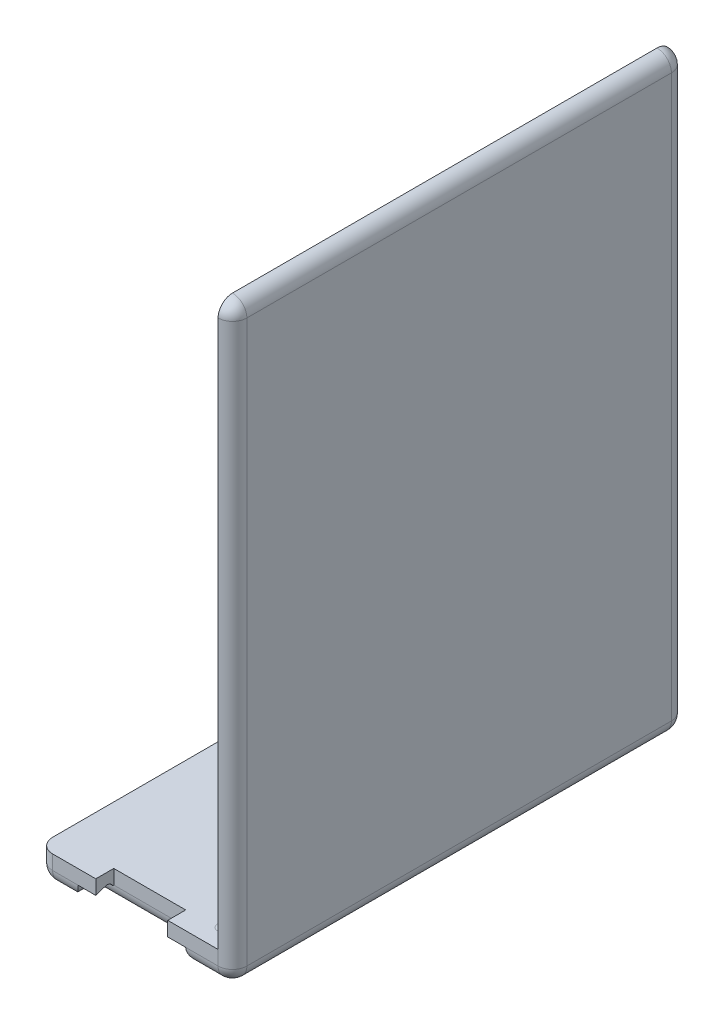
SolidWorks part; units mm, degrees
note: The reader was unsure of these and kept them because the rebuilt part matched: shared geometry of "Sketch6<3>".
ref_plane "Front Plane" through (0, 0, 0) normal (0, 0, 1) x (1, 0, 0)
ref_plane "Top Plane" through (0, 0, 0) normal (0, 1, 0) x (1, 0, 0)
ref_plane "Right Plane" through (0, 0, 0) normal (1, 0, 0) x (0, 0, -1)
sketch "Sketch1" plane through (0, 0, 0) normal (0, 1, 0) x (1, 0, 0)
  line L1 (0, 0) -> (-25, 0)
  line L2 (0, 0) -> (0, -63)
  line L3 (0, -63) -> (-25, -63)
  line L4 (-25, 0) -> (-25, -63)
  dimension "D1" = 63
  dimension "D2" = 25
extrude "Boss-Extrude1" add sketch "Sketch1" along normal blind 4
sketch "Sketch3" plane through (0, 0, 0) normal (1, 0, 0) x (0, 0, -1)
  line L1 (-63, 0) -> (0, 0)
  line L2 (-63, 0) -> (-63, 4)
  line L3 (-63, 4) -> (0, 4)
  line L4 (0, 0) -> (0, 4)
extrude "Boss-Extrude2" add sketch "Sketch3" along normal blind 2
sketch "Sketch4" plane through (0, 4, 0) normal (0, 1, 0) x (1, 0, 0)
  line L1 (2, -63) -> (0, -63)
  line L2 (2, -63) -> (2, 0)
  line L3 (2, 0) -> (0, 0)
  line L4 (0, -63) -> (0, 0)
extrude "Boss-Extrude3" add sketch "Sketch4" along normal blind 78
sketch "Sketch6" plane through (0, 0, 0) normal (0, -1, 0) x (1, 0, 0)
  line L0 (-25, 63) -> (2, 63) construction
  line L1 (-7, 63) -> (-17, 63)
  line L2 (-7, 63) -> (-7, 60.5)
  line L3 (-7, 60.5) -> (-17, 60.5)
  line L4 (-17, 63) -> (-17, 60.5)
  line L5 (2, 0) -> (-25, 0) construction
  line L6 (-7, 0) -> (-17, 0)
  line L7 (-7, 0) -> (-7, 2.5)
  line L8 (-7, 2.5) -> (-17, 2.5)
  line L9 (-17, 0) -> (-17, 2.5)
  line L10 (-25, 0) -> (-25, 63) construction
  dimension "D1" = 2.5
  dimension "D2" = 2.5
  dimension "D3" = 10
  dimension "D4" = 10
  dimension "D5" = 8
  dimension "D6" = 8
extrude "Cut-Extrude1" cut sketch "Sketch6" against normal through all contours L8 L9 L6 L7
extrude "Cut-Extrude2" cut sketch "Sketch6<3>" against normal blind 80 contours L3 L4 L1 L2
sketch "Sketch6<3>" plane through (0, 0, 0) normal (0, -1, 0) x (1, 0, 0) same geometry as "Sketch6"
sketch "Sketch8" plane through (0, 0, 63) normal (0, 0, 1) x (1, 0, 0)
  line L0 (-7, 0) -> (2, 0) construction
  line L1 (-4.5, 0) -> (-19.5, 0)
  line L2 (-4.5, 0) -> (-4.5, 2)
  line L3 (-4.5, 2) -> (-19.5, 2)
  line L4 (-19.5, 0) -> (-19.5, 2)
  line L5 (-25, 4) -> (-25, 0) construction
  dimension "D1" = 2
  dimension "D2" = 15
  dimension "D3" = 5.5
extrude "Cut-Extrude3" cut sketch "Sketch8" against normal blind 2.5
sketch "Sketch9" plane through (-4.5, 0, 0) normal (-1, 0, 0) x (0, 0, 1)
  line L0 (63, 0) -> (63, 2) construction
  line L1 (60.5, 2) -> (63, 2) construction
  line L2 (61.5, 2.5) -> (63, 2)
  line L3 (63, 2) -> (61.5, 2)
  line L4 (61.5, 2) -> (61.5, 2.5)
  circle A0 centre (61.5, 1.5) radius 1
  line M3 (63, 2) -> (60.5, 2)
  dimension "D1" = 2
  dimension "D2" = 1.5
  dimension "D3" = 0.5
extrude "Cut-Extrude5" cut sketch "Sketch9" along a picked direction on the side of the normal blind 15 contours A0 L3 M3 | L4 A0 M3
sketch "Sketch10" plane through (0, 0, 0) normal (0, -1, 0) x (1, 0, 0)
  line L0 (2, 31.5) -> (-25, 31.5) construction
  line L1 (2, 63) -> (2, 0) construction
  line L2 (-25, 0) -> (-25, 63) construction
  line L3 (-25, 31.5) -> (2, 31.5) construction
sketch "Sketch11" plane through (0, 0, 0) normal (0, 0, -1) x (-1, 0, 0)
  line L0 (-2, 0) -> (7, 0) construction
  line L1 (4.5, 0) -> (19.5, 0)
  line L2 (4.5, 0) -> (4.5, 2)
  line L3 (4.5, 2) -> (19.5, 2)
  line L4 (19.5, 0) -> (19.5, 2)
  line L5 (25, 4) -> (25, 0) construction
  dimension "D1" = 2
  dimension "D2" = 15
  dimension "D3" = 5.5
extrude "Cut-Extrude6" cut sketch "Sketch11" against normal blind 3 contours L2 L3 L4 L1
sketch "Sketch12" plane through (-4.5, 0, 0) normal (-1, 0, 0) x (0, 0, 1)
  line L0 (0, 0) -> (0, 2) construction
  line L1 (3, 2) -> (0, 2) construction
  line L2 (1.9, 2.5) -> (0, 2)
  line L3 (0, 2) -> (1.9, 2)
  line L4 (1.9, 2) -> (1.9, 2.5)
  circle A0 centre (1.9, 1.5) radius 1
  line M4 (3, 2) -> (0, 2)
  dimension "D1" = 2
  dimension "D2" = 1.9
  dimension "D3" = 0.5
extrude "Cut-Extrude7" cut sketch "Sketch12" along normal blind 15 contours A0 M4 | A0 L4 M4
fillet "Fillet6" radius 2 20 edges at (-22.25, 0, 0) (-12, 0, 3) (-19.5, 0, 1.5) (-4.5, 1, 0) (-4.5, 0, 1.5) (-19.5, 1, 3) (-4.5, 1, 3) (-19.5, 1, 0) (2, 0, 31.5) (-22.25, 0, 63) (-25, 0, 31.5) (-1.25, 0, 0) (-12, 0, 60.5) (-1.25, 0, 63) (-19.5, 1, 63) (-4.5, 1, 60.5) (-4.5, 0, 61.75) (-19.5, 1, 60.5) (-19.5, 0, 61.75) (-4.5, 1, 63)
fillet "Fillet7" radius 2 4 edges at (-24.4142, 0.5858, 62.4142) (-24.4142, 0.5858, 0.5858) (-25, 3, 63) (-25, 3, 0)
sketch "Sketch13" plane through (0, 4, 0) normal (0, 1, 0) x (1, 0, 0)
  line L6 (0, -4.25) -> (-1.5, -4.25)
  line L7 (0, 0) -> (0, -63) construction
  line L8 (-1.5, -4.25) -> (-1.5, -2.6)
  line L9 (-1.5, -2.6) -> (-2.7, -2.6)
  line L10 (-2.7, -2.6) -> (-2.7, -5.6)
  line L11 (-2.7, -5.6) -> (0, -5.6)
  line L12 (0, 0) -> (-7, 0) construction
  line L13 (0, -4.25) -> (0, -5.6)
  line L14 (0, -31.5) -> (-25.0562, -31.5) construction
  line L15 (-1.5, -60.4) -> (-2.7, -60.4)
  line L16 (-2.7, -60.4) -> (-2.7, -57.4)
  line L17 (-2.7, -57.4) -> (0, -57.4)
  line L18 (0, -58.75) -> (0, -57.4)
  line L19 (0, -58.75) -> (-1.5, -58.75)
  line L20 (-1.5, -58.75) -> (-1.5, -60.4)
  dimension "D1" = 1.5
  dimension "D2" = 1.2
  dimension "D3" = 2.6
  dimension "D4" = 3
  dimension "D5" = 1.35
extrude "Boss-Extrude4" add sketch "Sketch13" along normal blind 73
fillet "Fillet8" radius 0.4 24 edges at (-1.5, 4, 3.425) (0, 77, 4.925) (0, 77, 58.075) (-1.5, 4, 59.575) (-1.5, 40.5, 2.6) (-2.1, 77, 2.6) (-2.1, 4, 2.6) (-2.7, 40.5, 2.6) (-2.7, 77, 4.1) (-2.7, 4, 4.1) (-2.7, 40.5, 5.6) (-1.35, 77, 5.6) (0, 40.5, 5.6) (-1.35, 4, 5.6) (0, 40.5, 57.4) (-1.35, 77, 57.4) (-1.35, 4, 57.4) (-2.7, 40.5, 57.4) (-2.7, 77, 58.9) (-2.7, 4, 58.9) (-2.7, 40.5, 60.4) (-2.1, 77, 60.4) (-1.5, 40.5, 60.4) (-2.1, 4, 60.4)
fillet "Fillet9" radius 2 7 edges at (2, 42, 63) (2, 42, 0) (1.4142, 0.5858, 62.4142) (1.4142, 0.5858, 0.5858) (2, 82, 31.5) (1, 82, 0) (1, 82, 63)
sketch "Sketch14" plane through (0, 0, 0) normal (0, -1, 0) x (1, 0, 0)
  line L0 (-18.6192, 58.5) -> (-18.6192, 5) construction
  line L4 (-2.5, 58.5) -> (-21.5, 58.5) construction
  line L5 (-21.5, 5) -> (-2.5, 5) construction
  text T0 "RESP\r\n" font "Century Gothic" height in points 48
extrude "Cut-Extrude8" cut sketch "Sketch14" against normal blind 2
